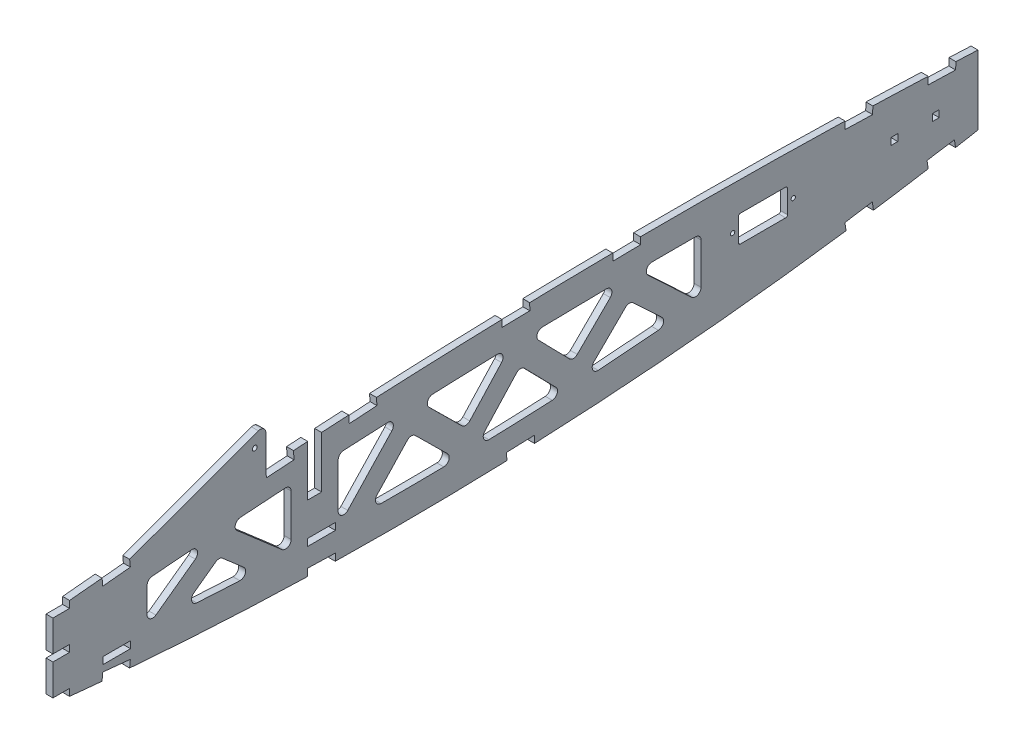
SolidWorks part; units mm, degrees
material "Balsa"
ref_plane "Front Plane" through (0, 0, 0) normal (0, 0, 1) x (1, 0, 0)
ref_plane "Top Plane" through (0, 0, 0) normal (0, 1, 0) x (1, 0, 0)
ref_plane "Right Plane" through (0, 0, 0) normal (1, 0, 0) x (0, 0, -1)
sketch "Sketch1" plane through (0, 0, 0) normal (1, 0, 0) x (0, 0, -1)
  line L1 (424.18, 29.337) -> (424.18, -2.413)
  line L2 (0, -15.875) -> (0, 15.875)
  line L3 (22.86, -10.922) -> (35.56, -10.922)
  line L4 (22.86, -10.922) -> (22.86, -14.097)
  line L5 (22.86, -14.097) -> (35.56, -14.097)
  line L6 (35.56, -10.922) -> (35.56, -14.097)
  line L7 (116.84, -14.097) -> (129.54, -14.097)
  line L8 (116.84, -14.097) -> (116.84, -10.922)
  line L9 (116.84, -10.922) -> (129.54, -10.922)
  line L10 (129.54, -14.097) -> (129.54, -10.922)
  line L11 (116.84, 4.318) -> (123.19, 4.318)
  line L12 (116.84, 4.318) -> (116.84, 27.6047)
  line L14 (123.19, 4.318) -> (123.19, 27.9734)
  line L22 (0, 15.875) -> (7.62, 15.875)
  line L23 (7.62, 15.875) -> (7.62, 19.05)
  line L24 (0, -15.875) -> (7.62, -15.875)
  line L25 (7.62, -15.875) -> (7.62, -19.05)
  line L27 (0, 1.5875) -> (7.62, 1.5875)
  line L28 (0, 1.5875) -> (0, -1.5875)
  line L29 (0, -1.5875) -> (7.62, -1.5875)
  line L30 (7.62, 1.5875) -> (7.62, -1.5875)
  arc A0 (7.62, 19.05) -> (424.18, 29.337) centre (286.6919, -2842.4417) cw
  arc A1 (7.62, -19.05) -> (424.18, -2.413) centre (157.1352, 1460.6321) ccw
  point P1 (215.7134, 31.75)
  point P2 (0, 0)
  point P3 (7.62, 0)
  point P4 (0, 0)
  point P26 (216.4858, -25.4)
  dimension "D2" = 7.62
  dimension "D3" = 31.75
  dimension "D4" = 424.18
  dimension "D5" = 38.1
  dimension "D6" = 10.922
  dimension "D7" = 3.175
  dimension "D8" = 12.7
  dimension "D9" = 3.175
  dimension "D10" = 81.28
  dimension "D11" = 15.24
  dimension "D13" = 31.75
  dimension "D14" = 116.84
  dimension "D15" = 25.4
  dimension "D16" = 6.35
  dimension "D17" = 13.462
extrude "Boss-Extrude1" add sketch "Sketch1" along normal blind 3.175 contours A1 L1 A0 L3 L6 L5 L4 L10 L7 L8 L9 L14 L11 L12 region at (0, 4.0025, -210.5119)
sketch "Sketch2" plane through (3.175, 0, 0) normal (1, 0, 0) x (0, 0, -1)
  line L0 (424.18, 29.337) -> (424.18, -2.413) construction
  line L1 (424.18, 29.337) -> (424.18, -2.413)
  line L2 (411.48, 17.2048) -> (411.48, 8.2174) construction
  line L3 (43.18, 9.5493) -> (43.18, -9.4747)
  line L6 (109.22, -13.106) -> (109.22, 14.4192)
  line L7 (164.2974, 7.1149) -> (163.989, 17.2702) construction
  line L12 (168.269, 17.4755) -> (189.3562, -3.3726)
  line L21 (130.81, 15.6785) -> (130.81, -13.6497)
  line L25 (189.3562, -3.3726) -> (209.7784, 18.8927)
  line L26 (144.5893, -13.8314) -> (164.2974, 7.1149)
  line L28 (164.2974, 7.1149) -> (185.2663, -13.6164)
  line L29 (130.81, 15.6785) -> (159.709, 17.0649)
  line L30 (209.7784, 18.8927) -> (218.5205, 19.1144) construction
  line L36 (214.3492, 8.8453) -> (234.5689, -11.8501)
  line L37 (218.5205, 19.1144) -> (238.6243, -1.4626)
  line L38 (238.6243, -1.4626) -> (260.0484, 19.8023)
  line L39 (243.0557, -11.3793) -> (264.2679, 9.6753)
  line L40 (297.18, -7.2192) -> (297.18, 19.9071)
  line L41 (260.0484, 19.8023) -> (268.2478, 19.8669) construction
  line L42 (164.2974, 7.1149) -> (171.4405, 14.3399)
  line L44 (193.9218, -13.4258) -> (214.3492, 8.8453)
  line L45 (264.2679, 9.6753) -> (283.6276, -8.4491)
  line L46 (297.18, -7.2192) -> (268.2478, 19.8669)
  line L47 (43.18, 9.5493) -> (72.601, 11.9086)
  line L48 (43.18, -9.4747) -> (72.601, 11.9086)
  line L49 (109.22, -13.106) -> (79.7712, 12.4373)
  line L50 (72.601, 11.9086) -> (79.7712, 12.4373) construction
  line L51 (79.7712, 12.4373) -> (109.22, 14.4192)
  line L52 (76.276, 2.0196) -> (76.276, 12.1796) construction
  line L53 (93.0033, -12.4894) -> (99.6606, -4.8143) construction
  line L54 (58.9007, -10.6088) -> (76.276, 2.0196)
  line L55 (76.276, 2.0196) -> (93.0033, -12.4894)
  line L57 (214.3492, 8.8453) -> (206.8618, 15.7129)
  line L58 (123.19, 4.318) -> (130.81, 4.318) construction
  line L60 (35.56, -14.097) -> (43.18, -14.097)
  line L61 (130.81, -13.6497) -> (159.709, 17.0649)
  line L62 (116.84, -10.922) -> (109.22, -10.922)
  line L63 (159.709, 17.0649) -> (168.269, 17.4755) construction
  line L64 (58.9007, -10.6088) -> (52.9274, -2.3902) construction
  line L66 (144.5893, -13.8314) -> (137.1897, -6.8692) construction
  line L67 (189.3562, -3.3726) -> (189.3562, -13.5326)
  line L68 (168.269, 17.4755) -> (209.7784, 18.8927) construction
  line L69 (238.6243, -1.4626) -> (231.3571, -8.5627) construction
  line L70 (264.2679, 9.6753) -> (257.1105, 16.8862) construction
  line L71 (264.2679, 9.6753) -> (271.2115, 17.0922) construction
  line L72 (214.3492, 8.8453) -> (214.0917, 19.0021) construction
  line L73 (238.6243, -1.4626) -> (238.8126, -11.6208) construction
  line L74 (264.2679, 9.6753) -> (264.1481, 19.8346)
  line L75 (180.3165, -13.7025) -> (238.8126, -11.6208) construction
  line L76 (238.8126, -11.6208) -> (297.18, -7.2192)
  line L77 (144.5893, -13.8314) -> (185.2663, -13.6164) construction
  line L78 (424.18, 13.462) -> (297.18, 13.462) construction
  line L79 (411.48, 24.257) -> (398.78, 24.257)
  line L80 (411.48, 24.257) -> (411.48, 21.082)
  line L81 (411.48, 21.082) -> (398.78, 21.082)
  line L82 (398.78, 24.257) -> (398.78, 21.082)
  line L83 (360.68, 24.257) -> (373.38, 24.257)
  line L84 (360.68, 24.257) -> (360.68, 21.082)
  line L85 (360.68, 21.082) -> (373.38, 21.082)
  line L86 (373.38, 24.257) -> (373.38, 21.082)
  line L87 (411.48, 5.842) -> (398.78, 5.842)
  line L88 (398.78, 2.667) -> (398.78, 5.842)
  line L89 (411.48, 2.667) -> (398.78, 2.667)
  line L90 (411.48, 2.667) -> (411.48, 5.842)
  line L91 (360.68, 5.842) -> (373.38, 5.842)
  line L92 (373.38, 2.667) -> (373.38, 5.842)
  line L93 (360.68, 2.667) -> (373.38, 2.667)
  line L94 (360.68, 2.667) -> (360.68, 5.842)
  line L95 (398.78, 21.082) -> (398.78, 13.462) construction
  line L96 (373.38, 21.082) -> (373.38, 13.462) construction
  line L97 (218.5205, 19.1144) -> (260.0484, 19.8023)
  line L104 (193.9218, -13.4258) -> (234.5689, -11.8501) construction
  line L105 (243.0557, -11.3793) -> (283.6276, -8.4491) construction
  line L106 (268.2478, 19.8669) -> (297.18, 19.9071) construction
  arc A0 (7.62, -19.05) -> (424.18, -2.413) centre (157.1352, 1460.6321) ccw construction
  arc A1 (424.18, 29.337) -> (123.19, 27.9734) centre (286.6919, -2842.4417) ccw construction
  arc A2 (7.62, -19.05) -> (424.18, -2.413) centre (157.1352, 1460.6321) ccw
  arc A3 (424.18, 29.337) -> (123.19, 27.9734) centre (286.6919, -2842.4417) ccw
  arc A4 (58.9007, -10.6088) -> (93.0033, -12.4894) centre (157.1352, 1460.6321) ccw
  arc A6 (43.18, -9.4747) -> (58.9007, -10.6088) centre (157.1352, 1460.6321) ccw construction
  arc A7 (43.18, 9.5493) -> (123.9122, 15.294) centre (286.6919, -2842.4417) ccw construction
  arc A8 (411.48, 17.2048) -> (123.9122, 15.294) centre (286.6919, -2842.4417) ccw construction
  arc A9 (8.8968, -6.4143) -> (43.18, -9.4747) centre (157.1352, 1460.6321) ccw construction
  arc A10 (8.8968, -6.4143) -> (411.48, 8.2174) centre (157.1352, 1460.6321) ccw construction
  arc A11 (144.5893, -13.8314) -> (185.2663, -13.6164) centre (157.1352, 1460.6321) ccw
  arc A12 (93.0033, -12.4894) -> (109.22, -13.106) centre (157.1352, 1460.6321) ccw construction
  arc A14 (243.0557, -11.3793) -> (283.6276, -8.4491) centre (157.1352, 1460.6321) ccw
  arc A15 (130.81, 15.6785) -> (109.22, 14.4192) centre (286.6919, -2842.4417) ccw construction
  arc A16 (109.22, -13.106) -> (130.81, -13.6497) centre (157.1352, 1460.6321) ccw construction
  arc A17 (130.81, -13.6497) -> (144.5893, -13.8314) centre (157.1352, 1460.6321) ccw construction
  arc A19 (185.2663, -13.6164) -> (318.3561, -5.0444) centre (157.1352, 1460.6321) ccw construction
  arc A20 (297.18, 19.9071) -> (268.2478, 19.8669) centre (286.6919, -2842.4417) ccw
  arc A21 (168.269, 17.4755) -> (130.81, 15.6785) centre (286.6919, -2842.4417) ccw construction
  arc A22 (109.22, 14.4192) -> (79.7712, 12.4373) centre (286.6919, -2842.4417) ccw
  arc A24 (180.3165, -13.7025) -> (193.9218, -13.4258) centre (157.1352, 1460.6321) ccw construction
  arc A28 (193.9218, -13.4258) -> (234.5689, -11.8501) centre (157.1352, 1460.6321) ccw
  arc A30 (209.7784, 18.8927) -> (168.269, 17.4755) centre (286.6919, -2842.4417) ccw
  arc A31 (297.18, -7.2192) -> (411.48, 8.2174) centre (157.1352, 1460.6321) ccw construction
  arc A32 (283.6276, -8.4491) -> (297.18, -7.2192) centre (157.1352, 1460.6321) ccw construction
  arc A33 (411.48, 17.2048) -> (297.18, 19.9071) centre (286.6919, -2842.4417) ccw construction
  arc A34 (234.5689, -11.8501) -> (243.0557, -11.3793) centre (157.1352, 1460.6321) ccw construction
  arc A36 (297.18, 19.9071) -> (268.2478, 19.8669) centre (286.6919, -2842.4417) ccw
  arc A37 (72.601, 11.9086) -> (43.18, 9.5493) centre (286.6919, -2842.4417) ccw
  point P48 (424.18, 13.462)
  dimension "D8" = 41.5279
  dimension "D3" = 10.16
  dimension "D4" = 7.62
  dimension "D5" = 10.16
  dimension "D6" = 7.62
  dimension "D7" = 63.5
  dimension "D9" = 25.4
  dimension "D13" = 12.7
  dimension "D14" = 3.175
  dimension "D25" = 7.62
  dimension "0.5" = 12.7
  dimension "D1" = 12.7
extrude "Cut-Extrude1" cut sketch "Sketch2" against normal through all contours L3 L48 L47 | L54 A4 L55 | L51 L49 L6 | L21 L61 L29 | L26 A11 L28 | L44 A28 L36 | L38 L97 L37 | L39 L76 L45 | L40 A20 L46 | L25 A30 L12 region at (3.175, 3.9944, -52.987) region at (3.175, 4.5835, -99.4037) region at (3.175, -5.5392, -214.2797) region at (3.175, -6.8399, -164.7195) region at (3.175, 6.3646, -140.443) region at (3.175, 12.4847, -239.0644) region at (3.175, 10.8678, -287.5273) region at (3.175, -3.2919, -263.6104) region at (3.175, -7.0701, -76.059)
fillet "Fillet1" radius 2.54 9 edges at (1.5875, 14.4192, -109.22) (1.5875, 12.4373, -79.7712) (1.5875, -13.106, -109.22) (1.5875, -12.4894, -93.0033) (1.5875, 2.0196, -76.276) (1.5875, -10.6088, -58.9007) (1.5875, -9.4747, -43.18) (1.5875, 11.9086, -72.601) (1.5875, 9.5493, -43.18)
fillet "Fillet2" radius 2.54 21 edges at (1.5875, -13.6164, -185.2663) (1.5875, 7.1149, -164.2974) (1.5875, -13.8314, -144.5893) (1.5875, -13.6497, -130.81) (1.5875, 17.0649, -159.709) (1.5875, 15.6785, -130.81) (1.5875, 19.9071, -297.18) (1.5875, 19.8669, -268.2478) (1.5875, -7.2192, -297.18) (1.5875, -8.2567, -283.4221) (1.5875, 9.6753, -264.2679) (1.5875, -11.2944, -243.1412) (1.5875, 19.8023, -260.0484) (1.5875, 19.1144, -218.5205) (1.5875, -1.4626, -238.6243) (1.5875, -11.8501, -234.5689) (1.5875, -13.4258, -193.9218) (1.5875, 8.8453, -214.3492) (1.5875, 18.8927, -209.7784) (1.5875, 17.4755, -168.269) (1.5875, -3.3726, -189.3562)
sketch "Sketch4" plane through (3.175, 0, 0) normal (1, 0, 0) x (0, 0, -1)
  line L1 (208.0212, -22.3557) -> (220.7137, -21.9202)
  line L2 (208.0212, -22.3557) -> (208.1363, -25.71)
  line L4 (220.7137, -21.9202) -> (220.8269, -25.2203)
  line L5 (207.9299, 31.5472) -> (208.0212, 28.2172) construction
  line L6 (208.0212, 28.2172) -> (220.7164, 28.5651) construction
  line L11 (220.6259, 31.8671) -> (220.7164, 28.5651) construction
  line L12 (199.9194, -13.2639) -> (228.9415, -12.1353) construction
  line L13 (22.5303, 20.465) -> (22.86, 17.0848)
  line L14 (297.18, -1.3619) -> (297.18, 17.3752) construction
  line L19 (22.86, 17.0848) -> (35.5, 18.3175)
  line L20 (35.5, 18.3175) -> (35.1795, 21.6039)
  line L22 (7.62, 19.05) -> (38.5374, 22.0653) construction
  line L23 (7.62, -19.05) -> (64.7874, -24.8265) construction
  line L24 (35.1637, -21.5747) -> (35.4957, -18.2894)
  line L25 (35.4957, -18.2894) -> (22.86, -17.0126)
  line L26 (22.86, -17.0126) -> (22.5097, -20.4789)
  line L34 (116.7503, -26.0363) -> (116.84, -22.7355)
  line L35 (116.84, -22.7355) -> (129.5353, -23.0804)
  line L37 (116.7503, -26.0363) -> (129.4471, -26.3812) construction
  line L39 (129.5353, -23.0804) -> (129.4471, -26.327)
  line L40 (208.1363, -25.71) -> (220.8269, -25.2745) construction
  line L41 (207.9299, 31.5472) -> (220.6259, 31.8952) construction
  line L42 (297.18, -1.3619) -> (297.18, 17.3752) construction
  line L43 (363.2659, 31.6064) -> (375.9606, 31.2401) construction
  line L44 (363.2659, 31.6064) -> (363.1685, 28.2296)
  line L45 (375.9606, 31.2401) -> (375.8632, 27.8633)
  line L46 (363.1685, 28.2296) -> (375.8632, 27.8633)
  line L47 (401.3452, 30.3393) -> (414.0399, 29.973)
  line L48 (401.3452, 30.3393) -> (401.2463, 26.9117)
  line L49 (414.0399, 29.973) -> (413.941, 26.5454)
  line L50 (401.2463, 26.9117) -> (413.941, 26.5454)
  line L51 (363.6623, -12.1749) -> (363.1685, -8.6534)
  line L52 (363.1685, -8.6534) -> (375.719, -6.7103)
  line L53 (375.719, -6.7103) -> (376.2616, -10.3531)
  line L54 (401.3524, -6.3961) -> (400.8203, -2.8242)
  line L55 (400.8203, -2.8242) -> (413.3708, -0.8811)
  line L56 (413.3708, -0.8811) -> (413.8737, -4.2567)
  line L57 (97.6302, 26.4033) -> (97.8808, 22.6015)
  line L58 (97.8808, 22.6015) -> (110.5533, 23.4367)
  line L59 (110.5533, 23.4367) -> (110.3046, 27.2104)
  line L60 (97.6302, 26.4033) -> (110.3046, 27.2385) construction
  line L62 (148.3498, 29.296) -> (148.5708, 25.9421)
  line L63 (148.5708, 25.9421) -> (135.8983, 25.107)
  line L64 (135.8983, 25.107) -> (135.6644, 28.6568)
  arc A1 (208.1363, -25.71) -> (220.8269, -25.2203) centre (157.1352, 1460.6321) ccw
  arc A2 (216.2243, 6.9262) -> (212.5356, 6.868) centre (214.4075, 5.1511) ccw construction
  arc A3 (199.9194, -13.2639) -> (228.9415, -12.1353) centre (157.1352, 1460.6321) ccw construction
  arc A4 (199.9194, -13.2639) -> (228.9415, -12.1353) centre (157.1352, 1460.6321) ccw construction
  arc A7 (116.84, 27.6047) -> (7.62, 19.05) centre (286.6919, -2842.4417) ccw construction
  arc A8 (220.6259, 31.8671) -> (207.9299, 31.5472) centre (286.6919, -2842.4417) ccw
  arc A9 (7.62, -19.05) -> (424.18, -2.413) centre (157.1352, 1460.6321) ccw construction
  arc A10 (22.5097, -20.4789) -> (35.1637, -21.5747) centre (157.1352, 1460.6321) ccw
  arc A11 (363.6623, -12.1749) -> (376.2616, -10.3531) centre (157.1352, 1460.6321) ccw
  arc A12 (414.0351, 29.8047) -> (401.3452, 30.3393) centre (286.6919, -2842.4417) ccw construction
  arc A13 (116.7503, -26.0363) -> (129.4471, -26.327) centre (157.1352, 1460.6321) ccw
  arc A14 (35.1795, 21.6039) -> (22.5303, 20.465) centre (286.6919, -2842.4417) ccw
  arc A16 (375.9606, 31.2401) -> (363.2659, 31.6064) centre (286.6919, -2842.4417) ccw
  arc A17 (401.3524, -6.3961) -> (413.8737, -4.2567) centre (157.1352, 1460.6321) ccw
  arc A18 (110.3046, 27.2104) -> (97.6302, 26.4033) centre (286.6919, -2842.4417) ccw
  arc A19 (135.6644, 28.6568) -> (148.3498, 29.296) centre (286.6919, -2842.4417) cw
  arc A20 (424.18, 29.337) -> (123.19, 27.9734) centre (286.6919, -2842.4417) ccw construction
  arc A23 (116.84, 27.6047) -> (7.62, 19.05) centre (286.6919, -2842.4417) ccw construction
  point P16 (214.3674, 7.6908)
  point P17 (214.3674, -22.138)
  dimension "D2" = 3.302
  dimension "D3" = 12.7
  dimension "D4" = 3.302
  dimension "D5" = 12.7
  dimension "D6" = 3.302
  dimension "0.5" = 12.7
  dimension "D7" = 12.7
  dimension "D8" = 6.5354
  dimension "D10" = 3.302
  dimension "D11" = 12.7
  dimension "D12" = 3.302
  dimension "D13" = 3.3782
  dimension "D14" = 3.429
  dimension "D15" = 12.7
  dimension "D16" = 25.4
  dimension "D17" = 10.16
  dimension "D18" = 12.7
  dimension "D19" = 3.556
  dimension "D20" = 3.683
  dimension "D21" = 12.7
  dimension "D22" = 25.4
  dimension "D24" = 12.7
  dimension "D25" = 3.81
  dimension "D26" = 12.7
  dimension "D27" = 25.4
extrude "Cut-Extrude2" cut sketch "Sketch4" against normal through all contours L48 L50 L49 L47 | L51 A11 L53 L52 | L2 A1 L4 L1 | L46 L45 A16 L44 | L55 L56 A17 L54 | L25 L26 A10 L24 | L19 L20 A14 L13 | L58 L59 A18 L57 | L63 L64 A19 L62 | L35 L39 A13 L34 region at (3.175, -23.8067, -214.4075) region at (3.175, 28.4423, -407.6431) region at (3.175, -9.4726, -369.7403)
sketch "Sketch5" plane through (0, 0, 0) normal (-1, 0, 0) x (0, 0, 1)
  line L0 (-403.225, 11.3792) -> (-406.4, 11.3792) construction
  line L1 (-406.4, 11.3792) -> (-406.4, 14.5542) construction
  line L2 (-406.4, 14.5542) -> (-403.225, 14.5542) construction
  line L3 (-403.225, 14.5542) -> (-403.225, 11.3792) construction
  line L4 (-384.2211, 14.5542) -> (-384.2211, 11.3792) construction
  line L5 (-384.2211, 11.3792) -> (-387.3961, 11.3792) construction
  line L6 (-387.3961, 11.3792) -> (-387.3961, 14.5542) construction
  line L7 (-387.3961, 14.5542) -> (-384.2211, 14.5542) construction
  line L8 (-403.225, 11.3792) -> (-406.4, 11.3792)
  line L9 (-406.4, 11.3792) -> (-406.4, 14.5542)
  line L10 (-406.4, 14.5542) -> (-403.225, 14.5542)
  line L11 (-403.225, 14.5542) -> (-403.225, 11.3792)
  line L12 (-384.2211, 14.5542) -> (-384.2211, 11.3792)
  line L13 (-384.2211, 11.3792) -> (-387.3961, 11.3792)
  line L14 (-387.3961, 11.3792) -> (-387.3961, 14.5542)
  line L15 (-387.3961, 14.5542) -> (-384.2211, 14.5542)
extrude "Cut-Extrude3" cut sketch "Sketch5" against normal up to surface (3.175 mm away) up to face at (3.175, 6.9553, -139.8703)
sketch "Sketch6" plane through (0, 0, 0) normal (1, 0, 0) x (0, 0, -1)
  line L0 (97.6302, 44.3341) -> (35.1795, 44.3341) construction
  line L1 (35.1795, 21.6039) -> (97.6302, 44.3341)
  line L3 (97.6302, 44.3341) -> (97.6302, 26.4033)
  circle A0 centre (92.5502, 37.0791) radius 1.1
  arc A6 (97.6302, 26.4033) -> (35.1795, 21.6039) centre (286.6919, -2842.4417) ccw construction
  arc A7 (97.6302, 26.4033) -> (35.1795, 21.6039) centre (286.6919, -2842.4417) ccw
  dimension "D2" = 2.2
  dimension "D4" = 5.08
  dimension "D1" = 20
  dimension "0.25" = 5.08
extrude "Boss-Extrude2" add sketch "Sketch6" along normal blind 3.175 contours A7 L3 L1 A0 region at (0, 30.8239, -76.8395)
fillet "Fillet3" radius 2.54 1 edges at (1.5875, 44.3341, -97.6302)
sketch "Sketch7" plane through (3.175, 0, 0) normal (1, 0, 0) x (0, 0, -1)
  line L0 (269.4641, 29.3998) -> (256.766, 29.1832) construction
  line L1 (256.766, 29.1832) -> (256.7118, 32.3578) construction
  line L2 (256.7118, 32.3578) -> (256.658, 35.5172)
  line L3 (269.41, 32.5743) -> (269.4641, 29.3998) construction
  line L4 (218.6715, 28.5335) -> (205.9734, 28.3169) construction
  line L5 (205.9734, 28.3169) -> (205.9192, 31.4914) construction
  line L6 (205.9192, 31.4914) -> (205.8669, 34.5593)
  line L7 (218.6174, 31.708) -> (218.6715, 28.5335) construction
  line L8 (269.4641, 29.3998) -> (256.766, 29.1832)
  line L9 (256.766, 29.1832) -> (256.7118, 32.3578)
  line L11 (269.41, 32.5743) -> (269.4641, 29.3998)
  line L12 (218.6715, 28.5335) -> (205.9734, 28.3169)
  line L13 (205.9734, 28.3169) -> (205.9192, 31.4914)
  line L15 (218.6174, 31.708) -> (218.6715, 28.5335)
  line L16 (218.6174, 31.708) -> (218.6174, 31.9687)
  line L17 (205.8669, 34.5593) -> (218.5695, 34.7759)
  line L18 (218.5695, 34.7759) -> (218.6174, 31.9687)
  line L19 (256.658, 35.5172) -> (269.3561, 35.7338)
  line L20 (269.3561, 35.7338) -> (269.41, 32.5743)
  line L21 (336.825, 7.6492) -> (336.825, 18.1492) construction
  line L22 (315.175, 6.7992) -> (335.975, 6.7992) construction
  line L23 (314.325, 18.1492) -> (314.325, 7.6492) construction
  line L24 (335.975, 18.9992) -> (315.175, 18.9992) construction
  line L25 (336.825, 7.6492) -> (336.825, 18.1492)
  line L26 (315.175, 6.7992) -> (335.975, 6.7992)
  line L27 (314.325, 18.1492) -> (314.325, 7.6492)
  line L28 (335.975, 18.9992) -> (315.175, 18.9992)
  arc A0 (311.675, 11.9197) -> (312.6545, 12.8992) centre (311.675, 12.8992) ccw construction
  arc A1 (311.675, 13.8787) -> (310.6955, 12.8992) centre (311.675, 12.8992) ccw construction
  arc A2 (312.6545, 12.8992) -> (311.675, 13.8787) centre (311.675, 12.8992) ccw construction
  arc A3 (310.6955, 12.8992) -> (311.675, 11.9197) centre (311.675, 12.8992) ccw construction
  arc A4 (339.475, 13.8787) -> (338.4955, 12.8992) centre (339.475, 12.8992) ccw construction
  arc A5 (340.4545, 12.8992) -> (339.475, 13.8787) centre (339.475, 12.8992) ccw construction
  arc A6 (339.475, 11.9197) -> (340.4545, 12.8992) centre (339.475, 12.8992) ccw construction
  arc A7 (338.4955, 12.8992) -> (339.475, 11.9197) centre (339.475, 12.8992) ccw construction
  arc A8 (336.825, 18.1492) -> (335.975, 18.9992) centre (335.975, 18.1492) ccw construction
  arc A9 (335.975, 6.7992) -> (336.825, 7.6492) centre (335.975, 7.6492) ccw construction
  arc A10 (314.325, 7.6492) -> (315.175, 6.7992) centre (315.175, 7.6492) ccw construction
  arc A11 (315.175, 18.9992) -> (314.325, 18.1492) centre (315.175, 18.1492) ccw construction
  arc A12 (311.675, 11.9197) -> (312.6545, 12.8992) centre (311.675, 12.8992) ccw
  arc A13 (311.675, 13.8787) -> (310.6955, 12.8992) centre (311.675, 12.8992) ccw
  arc A14 (312.6545, 12.8992) -> (311.675, 13.8787) centre (311.675, 12.8992) ccw
  arc A15 (310.6955, 12.8992) -> (311.675, 11.9197) centre (311.675, 12.8992) ccw
  arc A16 (339.475, 13.8787) -> (338.4955, 12.8992) centre (339.475, 12.8992) ccw
  arc A17 (340.4545, 12.8992) -> (339.475, 13.8787) centre (339.475, 12.8992) ccw
  arc A18 (339.475, 11.9197) -> (340.4545, 12.8992) centre (339.475, 12.8992) ccw
  arc A19 (338.4955, 12.8992) -> (339.475, 11.9197) centre (339.475, 12.8992) ccw
  arc A20 (336.825, 18.1492) -> (335.975, 18.9992) centre (335.975, 18.1492) ccw
  arc A21 (335.975, 6.7992) -> (336.825, 7.6492) centre (335.975, 7.6492) ccw
  arc A22 (314.325, 7.6492) -> (315.175, 6.7992) centre (315.175, 7.6492) ccw
  arc A23 (315.175, 18.9992) -> (314.325, 18.1492) centre (315.175, 18.1492) ccw
  dimension "D1" = 2.8072
  dimension "D2" = 0.2607
  dimension "D3" = 3.1594
extrude "Cut-Extrude8" cut sketch "Sketch7" against normal through all
